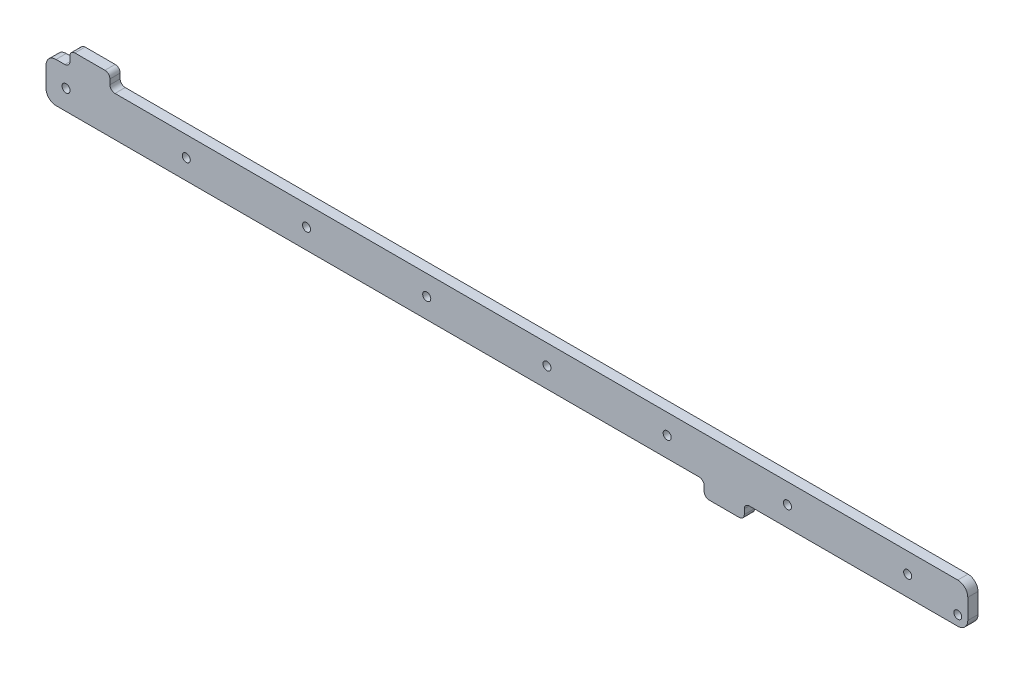
SolidWorks part; units mm, degrees
material "PC High Viscosity"
ref_plane "Front Plane" through (0, 0, 0) normal (0, 0, 1) x (1, 0, 0)
ref_plane "Top Plane" through (0, 0, 0) normal (0, 1, 0) x (1, 0, 0)
ref_plane "Right Plane" through (0, 0, 0) normal (1, 0, 0) x (0, 0, -1)
sketch "Sketch1" plane through (0, 0, 0) normal (0, 0, 1) x (1, 0, 0)
  line L1 (0, 0) -> (40.5308, 0)
  line L2 (0, 0) -> (0, 25.4)
  line L3 (0, 25.4) -> (15.1308, 25.4)
  line L4 (584.2, 0) -> (584.2, 25.4)
  line L5 (15.1308, 34.925) -> (40.5308, 34.925)
  line L6 (40.5308, 34.925) -> (40.5308, 25.4)
  line L7 (15.1308, 34.925) -> (15.1308, 25.4)
  line L11 (584.2, 10.0162) -> (577.85, 13.6823) construction
  line L12 (577.85, 13.6823) -> (571.5, 10.0162) construction
  line L13 (571.5, 10.0162) -> (571.5, 2.6838) construction
  line L14 (571.5, 2.6838) -> (577.85, -0.9823) construction
  line L15 (577.85, -0.9823) -> (584.2, 2.6838) construction
  line L16 (584.2, 2.6838) -> (584.2, 10.0162) construction
  line L19 (417.1409, 0) -> (417.1409, -9.525)
  line L20 (417.1409, -9.525) -> (442.5409, -9.525)
  line L21 (442.5409, -9.525) -> (442.5409, 0)
  line L22 (40.5308, 25.4) -> (584.2, 25.4)
  line L23 (40.5308, 0) -> (417.1409, 0)
  line L24 (442.5409, 0) -> (584.2, 0)
  circle A0 centre (577.85, 6.35) radius 2.4892
  circle A1 centre (577.85, 6.35) radius 6.35 construction
  point P24 (417.1409, -4.7625)
  dimension "D5" = 4.9784
  dimension "D6" = 9.525
  dimension "D7" = 12.7
  dimension "D1" = 584.2
  dimension "D2" = 25.4
  dimension "D3" = 25.4
  dimension "D4" = 167.0591
  dimension "D8" = 40.5308
  dimension "D9" = 25.4
extrude "Boss-Extrude1" add sketch "Sketch1" along normal blind 6.477 contours L6 L5 L3 | L1 L4 L3 L2 A0 | L1 region at (289.7362, 12.7081, 0)
fillet "Fillet2" radius 6.35 4 edges at (0, 0, 3.2385) (0, 25.4, 3.2385) (584.2, 25.4, 3.2385) (584.2, 0, 3.2385)
sketch "Sketch2" plane through (0, 0, 6.477) normal (0, 0, 1) x (1, 0, 0)
  line L0 (6.35, 25.4) -> (15.1308, 25.4) construction
  line L1 (584.2, 19.05) -> (584.2, 6.35) construction
  circle A0 centre (546.1, 12.7) radius 2.0193
  dimension "D1" = 4.0386
  dimension "D2" = 12.7
  dimension "D3" = 38.1
hole_wizard "CSK for #10 Flat Head Machine Screw (100)1" positions "Sketch4" profile "Sketch5" countersink size "#10" standard "ANSI Inch" end condition through all
sketch "Sketch4" plane through (0, 0, 6.477) normal (0, 0, 1) x (1, 0, 0)
  line L0 (584.2, 12.7) -> (0, 12.7) construction
  line L1 (584.2, 19.05) -> (584.2, 6.35) construction
  line L2 (0, 6.35) -> (0, 19.05) construction
  line L3 (6.35, 25.4) -> (15.1308, 25.4) construction
  point P11 (546.1, 12.7)
  dimension "D1" = 12.7
  dimension "D2" = 38.1
sketch "Sketch5" plane through (546.1, 12.7, 6.477) normal (1, 0, 0) x (0, -1, 0)
  line L0 (0, 0) -> (0, 6.477)
  line L1 (0, 6.477) -> (2.5527, 6.477)
  line L2 (2.5527, 6.477) -> (2.5527, 1.9608)
  line L3 (2.5527, 1.9608) -> (4.8895, 0)
  line L5 (4.8895, 0) -> (0, 0)
  line L6 (-2.5527, 1.9608) -> (-4.8895, 0) construction
  line L11 (0, -6.35) -> (0, 107.95) construction
  dimension "Thru Hole Dia." = 5.1054
  dimension "Thru Hole Depth" = 6.477
  dimension "Near C'Sink Dia." = 9.779
  dimension "Near C'Sink Angle" = 100
pattern_linear "LPattern1" count 8 spacing 76.2 along (-1, 0, 0) of "CSK for #10 Flat Head Machine Screw (100)1"
mirror "Mirror2" about plane through (0, 0, 0) normal (0, 0, 1) of bodies 108
delete or keep bodies "Body-Delete/Keep 1" type delete bodies bodies 108
fillet "Fillet3" radius 3.175 8 edges at (442.5409, 0, -3.2385) (442.5409, -9.525, -3.2385) (417.1409, -9.525, -3.2385) (417.1409, 0, -3.2385) (40.5308, 25.4, -3.2385) (40.5308, 34.925, -3.2385) (15.1308, 34.925, -3.2385) (15.1308, 25.4, -3.2385)
